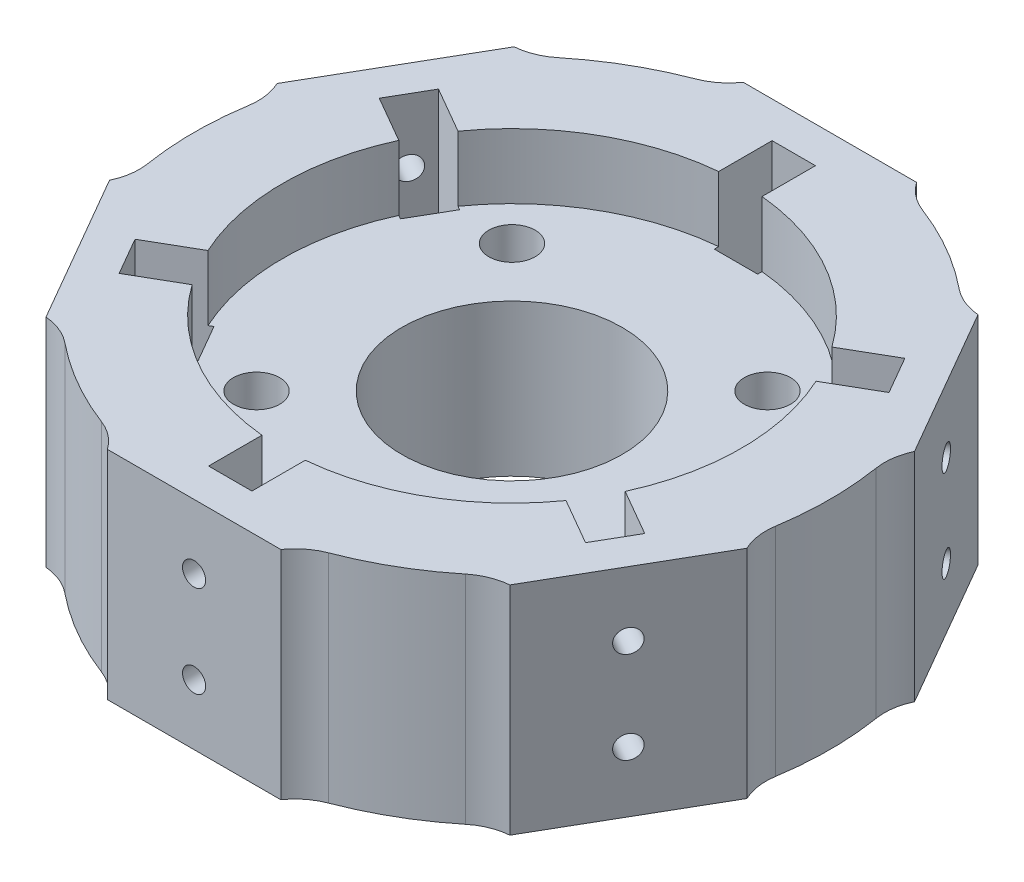
SolidWorks part; units mm, degrees
note: '?' marks a value the reader was unsure of.
material "PP Copolymer"
ref_plane "Front Plane" through (0, 0, 0) normal (0, 0, 1) x (1, 0, 0)
ref_plane "Top Plane" through (0, 0, 0) normal (0, 1, 0) x (1, 0, 0)
ref_plane "Right Plane" through (0, 0, 0) normal (1, 0, 0) x (0, 0, -1)
sketch "Sketch2" plane through (0, 0, 0) normal (0, 1, 0) x (1, 0, 0)
  line L0 (-12, 44) -> (12, 44)
  line L1 (-12, 44) -> (0, 0)
  line L2 (0, 0) -> (32.1051, 32.3923)
  line L3 (-2.875, 39) -> (2.875, 39) construction
  line L4 (-3.125, 38.75) -> (-3.125, 33.75) construction
  line L5 (-2.875, 33.5) -> (2.875, 33.5) construction
  line L6 (3.125, 38.75) -> (3.125, 33.75) construction
  line L7 (0, -44) -> (0, 44) construction
  line L9 (0, -16.5) -> (0, 16.5) construction
  arc A0 (12, 44) -> (15.7078, 41.1007) centre (18.5638, 48.5735) ccw
  arc A1 (32.1051, 32.3923) -> (27.7403, 34.1537) centre (32.784, 40.3634) cw
  arc A2 (15.7078, 41.1007) -> (27.7403, 34.1537) centre (0, 0) cw
  arc A3 (-3.125, 33.75) -> (-2.875, 33.5) centre (-2.875, 33.75) ccw construction
  arc A4 (2.875, 33.5) -> (3.125, 33.75) centre (2.875, 33.75) ccw construction
  arc A5 (2.875, 39) -> (3.125, 38.75) centre (2.875, 38.75) cw construction
  arc A6 (-2.875, 39) -> (-3.125, 38.75) centre (-2.875, 38.75) ccw construction
  circle A7 centre (0, 0) radius 45.607 construction
  point P19 (0, 0)
  point P20 (0, 39)
  dimension "D1" = 24
  dimension "D3" = 44
  dimension "D4" = 8
  dimension "D6" = 0.25
  dimension "D10" = 91.214
  dimension "D2" = 88
  dimension "D5" = 60
  dimension "D7" = 5.75
  dimension "D8" = 5
  dimension "D9" = 5
extrude "Boss-Extrude1" add sketch "Sketch2" against normal blind 30
hole_wizard "M3 Clearance Hole - Plastic Parts Only" positions "Sketch8" profile "Sketch9" hole size "M3" standard "ANSI Metric"
sketch "Sketch8" plane through (0, 0, -44) normal (0, 0, -1) x (-1, 0, 0)
  line L0 (0, -20.018) -> (0, -10.518) construction
  line L1 (0, -8.918) -> (0, 0) construction
  line L4 (0, -21.618) -> (0, -30) construction
  line L6 (0, -30) -> (0, -40.16) construction
  line L7 (-12, -30) -> (12, -30) construction
  circle A0 centre (0, -8.918) radius 1.6 construction
  circle A1 centre (0, -21.618) radius 1.6 construction
  point P0 (0, -8.918)
  point P2 (0, -21.618)
  dimension "D1" = 3.2
  dimension "D2" = 9.5
  dimension "D3" = 12.7
  dimension "D4" = 8.918
  dimension "D5" = 18.542
  dimension "D6" = 8.382
sketch "Sketch9" plane through (0, -8.918, -44) normal (1, 0, 0) x (0, 1, 0)
  line L0 (0, 0) -> (0, 10.9614)
  line L1 (0, 10.9614) -> (1.6, 10)
  line L2 (1.6, 10) -> (1.6, 0)
  line L5 (1.6, 0) -> (0, 0)
  line L10 (0, 10.9614) -> (-1.6, 10) construction
  line L11 (0, -6.35) -> (0, 107.95) construction
  dimension "Hole Dia." = 3.2
  dimension "Hole Depth" = 10
  dimension "Drill Angle" = 118
sketch "Sketch10" plane through (0, 0, -44) normal (0, 0, -1) x (-1, 0, 0)
  line L0 (-3, 0) -> (-3, -30)
  line L1 (2.75, -7.3303) -> (0, -5.7426) construction
  line L2 (0, -5.7426) -> (-2.75, -7.3303) construction
  line L3 (-2.75, -7.3303) -> (-2.75, -10.5057) construction
  line L4 (-2.75, -10.5057) -> (0, -12.0934) construction
  line L5 (0, -12.0934) -> (2.75, -10.5057) construction
  line L6 (2.75, -10.5057) -> (2.75, -7.3303) construction
  line L7 (2.75, -23.2057) -> (2.75, -20.0303) construction
  line L8 (2.75, -20.0303) -> (0, -18.4426) construction
  line L9 (0, -18.4426) -> (-2.75, -20.0303) construction
  line L10 (-2.75, -20.0303) -> (-2.75, -23.2057) construction
  line L11 (-2.75, -23.2057) -> (0, -24.7934) construction
  line L12 (0, -24.7934) -> (2.75, -23.2057) construction
  line L13 (-3, -30) -> (3, -30)
  line L14 (3, -30) -> (3, 0)
  line L15 (3, 0) -> (-3, 0)
  line L21 (-12, -30) -> (12, -30) construction
  circle A0 centre (0, -8.918) radius 2.75 construction
  circle A1 centre (0, -21.618) radius 2.75 construction
  point P25 (0, 0)
  dimension "D1" = 5.5
  dimension "D2" = 6
extrude "Wrench Clearance Slots - Plastic Parts Only" cut sketch "Sketch10" against normal blind 8 from offset 5 offset against normal yes
hole_wizard "M3x0.5 Tapped Hole - Metal Parts Only" [suppressed] positions "Sketch13" profile "Sketch14" tap size "M3x0.5" standard "ANSI Metric"
sketch "Sketch13" plane through (0, 0, -44) normal (0, 0, -1) x (-1, 0, 0)
  point P0 (0, -8.325)
  point P3 (0, -21.675)
sketch "Sketch14" plane through (0, -8.325, -44) normal (1, 0, 0) x (0, 1, 0)
  line L0 (0, 0) -> (0, 8.2517)
  line L1 (0, 8.2517) -> (1.25, 7.5006)
  line L2 (1.25, 7.5006) -> (1.25, 0.5)
  line L3 (1.25, 0.5) -> (1.75, 0)
  line L5 (1.75, 0) -> (0, 0)
  line L6 (-1.25, 0.5) -> (-1.75, 0) construction
  line L10 (0, 8.2517) -> (-1.25, 7.5006) construction
  line L11 (0, -6.35) -> (0, 107.95) construction
  dimension "Tap Drill Dia." = 2.5
  dimension "Tap Drill Depth" = 7.5006
  dimension "Near C'Sink Dia." = 3.5
  dimension "Near C'Sink Angle" = 90
  dimension "Drill Angle" = 118
cosmetic thread "Hole Thread3" [suppressed] parameters "D1"=5.9995, "D2"=3
cosmetic thread "Hole Thread4" [suppressed] parameters "D1"=5.9995, "D2"=3
ref_axis "Centerline" through (0, 1.5, 0) along (0, -1, 0)?
pattern_circular "Body Revolve - Plastic Parts Only" count 6 over 360 about axis through (0, 0, 0) along (0, 1, 0) of "Boss-Extrude1", "M3 Clearance Hole - Plastic Parts Only", "Wrench Clearance Slots - Plastic Parts Only"
pattern_circular "Body Revolve - Metal Parts Only" [suppressed] count 6 over 360 about axis through (0, 1.5, 0) along (0, -1, 0)
cosmetic thread "Hole Thread5" [suppressed] parameters "D1"=5.9995, "D2"=3
cosmetic thread "Hole Thread6" [suppressed] parameters "D1"=5.9995, "D2"=3
cosmetic thread "Hole Thread7" [suppressed] parameters "D1"=5.9995, "D2"=3
cosmetic thread "Hole Thread8" [suppressed] parameters "D1"=5.9995, "D2"=3
cosmetic thread "Hole Thread9" [suppressed] parameters "D1"=5.9995, "D2"=3
cosmetic thread "Hole Thread10" [suppressed] parameters "D1"=5.9995, "D2"=3
cosmetic thread "Hole Thread11" [suppressed] parameters "D1"=5.9995, "D2"=3
cosmetic thread "Hole Thread12" [suppressed] parameters "D1"=5.9995, "D2"=3
cosmetic thread "Hole Thread13" [suppressed] parameters "D1"=5.9995, "D2"=3
cosmetic thread "Hole Thread14" [suppressed] parameters "D1"=5.9995, "D2"=3
sketch "Sketch3" plane through (0, 0, 0) normal (0, 0, 1) x (1, 0, 0)
  line L0 (0, 0) -> (0, -30)
  line L1 (0, -30) -> (15.25, -30)
  line L2 (15.25, -30) -> (15.25, -9)
  line L3 (15.25, -9) -> (31.75, -9)
  line L4 (31.75, -9) -> (31.75, 0)
  line L5 (31.75, 0) -> (0, 0)
  line L7 (0, -948.6801) -> (0, 49051.3199) construction
  line L8 (0, 1.5) -> (0, -31.5) construction
  line L9 (-15.7078, -30) -> (-12, -30) construction
  line L10 (-25.3468, 0) -> (-28.3468, 0) construction
  dimension "D1" = 63.5
  dimension "D2" = 30.5
  dimension "D3" = 9
revolve "End of Arm Flange Clearance" cut sketch "Sketch3" angle 360 about L7
hole_wizard "Mounting Screws" positions "Sketch4" profile "Sketch5" counterbore size "M6" standard "ANSI Metric" end condition up to next
sketch "Sketch4" plane through (0, -30, 0) normal (0, -1, 0) x (-1, 0, 0)
  line L0 (-17.6777, -17.6777) -> (-17.6777, 17.6777) construction
  line L1 (-17.6777, 17.6777) -> (17.6777, 17.6777) construction
  line L2 (17.6777, 17.6777) -> (17.6777, -17.6777) construction
  line L6 (17.6777, -17.6777) -> (-17.6777, -17.6777) construction
  line L8 (0, -17.6777) -> (0, -25) construction
  circle A0 centre (0, 0) radius 25 construction
  point P0 (-17.6777, -17.6777)
  point P2 (-17.6777, 17.6777)
  point P4 (17.6777, 17.6777)
  point P6 (17.6777, -17.6777)
  dimension "D1" = 50
sketch "Sketch5" plane through (17.6777, -30, 17.6777) normal (1, 0, 0) x (0, 0, -1)
  line L0 (0, 0) -> (0, 21)
  line L1 (0, 21) -> (3.2, 21)
  line L3 (3.2, 21) -> (3.2, 6.5)
  line L4 (3.2, 6.5) -> (5.5, 6.5)
  line L5 (5.5, 6.5) -> (5.5, 0)
  line L7 (5.5, 0) -> (0, 0)
  line L11 (0, -6.35) -> (0, 107.95) construction
  dimension "Thru Hole Dia." = 6.4
  dimension "Thru Hole Depth" = 21
  dimension "C'Bore Dia." = 11
  dimension "C'Bore Depth" = 6.5
hole_wizard "Locating Pin" positions "Sketch6" profile "Sketch7" hole size "Ø6.0" standard "ANSI Metric" end condition up to next
sketch "Sketch6" plane through (0, -30, 0) normal (0, -1, 0) x (-1, 0, 0)
  circle A0 centre (0, 0) radius 25 construction
  point P2 (0, -25)
sketch "Sketch7" plane through (0, -30, 25) normal (1, 0, 0) x (0, 0, -1)
  line L0 (0, 0) -> (0, 21)
  line L1 (0, 21) -> (3.15, 21)
  line L2 (3.15, 21) -> (3.15, 0)
  line L5 (3.15, 0) -> (0, 0)
  line L11 (0, -6.35) -> (0, 107.95) construction
  dimension "Thru Hole Dia." = 6.3
  dimension "Thru Hole Depth" = 21
sketch "Sketch11" [suppressed] plane through (0, 0, 0) normal (0, 1, 0) x (1, 0, 0)
  line L0 (-32.3923, 32.1051) -> (-11.6077, 44.1051) construction
  line L1 (-24.7063, 36.5426) -> (-19.2937, 39.6676) construction
  line L2 (-24.7063, 36.5426) -> (-18.4414, 25.6915) construction
  line L3 (-18.4414, 25.6915) -> (-13.0288, 28.8165) construction
  line L4 (-19.2937, 39.6676) -> (-13.0288, 28.8165) construction
  line L5 (-22.0813, 31.996) -> (-19.5813, 27.6659) construction
  line L6 (-16.6687, 35.121) -> (-14.1687, 30.7909) construction
  line L7 (19.2937, 39.6676) -> (24.7063, 36.5426) construction
  line L8 (19.2937, 39.6676) -> (13.0288, 28.8165) construction
  line L9 (13.0288, 28.8165) -> (18.4414, 25.6915) construction
  line L10 (24.7063, 36.5426) -> (18.4414, 25.6915) construction
  line L11 (44, 3.125) -> (44, -3.125) construction
  line L12 (44, 3.125) -> (31.4702, 3.125) construction
  line L13 (31.4702, 3.125) -> (31.4702, -3.125) construction
  line L14 (44, -3.125) -> (31.4702, -3.125) construction
  line L15 (24.7063, -36.5426) -> (19.2937, -39.6676) construction
  line L16 (24.7063, -36.5426) -> (18.4414, -25.6915) construction
  line L17 (18.4414, -25.6915) -> (13.0288, -28.8165) construction
  line L18 (19.2937, -39.6676) -> (13.0288, -28.8165) construction
  line L19 (-19.2937, -39.6676) -> (-24.7063, -36.5426) construction
  line L20 (-19.2937, -39.6676) -> (-13.0288, -28.8165) construction
  line L21 (-13.0288, -28.8165) -> (-18.4414, -25.6915) construction
  line L22 (-24.7063, -36.5426) -> (-18.4414, -25.6915) construction
  line L23 (-44, -3.125) -> (-44, 3.125) construction
  line L24 (-44, -3.125) -> (-31.4702, -3.125) construction
  line L25 (-31.4702, -3.125) -> (-31.4702, 3.125) construction
  line L26 (-44, 3.125) -> (-31.4702, 3.125) construction
  line L27 (-13.0288, 28.8165) -> (13.0288, 28.8165)
  line L28 (-15.7351, 27.254) -> (0, 0) construction
  line L29 (0, 0) -> (15.7351, 27.254) construction
  line L30 (0, 41.46) -> (0, 44) construction
  arc A0 (-13.0288, 28.8165) -> (13.0288, 28.8165) centre (0, 28.4253) cw
  circle A1 centre (0, 0) radius 31.625 construction
  arc A2 (6.947, 43.4481) -> (-6.947, 43.4481) centre (0, 0) ccw construction
  point P15 (22, 38.1051)
  point P37 (0, 0)
  point P44 (0, 44)
  dimension "D3" = 13.0347
  dimension "D2" = 2.54
  dimension "D1" = 6
extrude "Lightnening Cut - Walls - Metal Parts Only" [suppressed] cut sketch "Sketch11" against normal up to surface (9 mm away)
pattern_circular "Ligntening Cut - Walls - Pattern - Metal Parts Only" [suppressed] count 6 over 360
sketch "Sketch12" [suppressed] plane through (0, -9, 0) normal (0, 1, 0) x (1, 0, 0)
  line L0 (5.5433, -22.7039) -> (11.662, -20.1694) construction
  arc A5 (13.0288, 28.8165) -> (11.5791, 19.9267) centre (-10.6033, 28.107) cw
  arc A6 (-11.5791, -19.9267) -> (-13.0288, -28.8165) centre (10.6033, -28.107) ccw
  arc A12 (-11.5791, -19.9267) -> (-23.8705, -19.6521) centre (-17.6777, -17.6777) ccw
  circle A13 centre (8.6026, -21.4367) radius 3.3114 construction
  arc A14 (23.8705, -19.6521) -> (11.5791, -19.9267) centre (17.6777, -17.6777) ccw
  arc A15 (11.5791, 19.9267) -> (23.8705, 19.6521) centre (17.6777, 17.6777) ccw
  arc A16 (-23.8705, 19.6521) -> (-11.5791, 19.9267) centre (-17.6777, 17.6777) ccw
  arc A17 (-11.5791, 19.9267) -> (-23.8705, 19.6521) centre (-17.6777, 17.6777) ccw construction
  arc A19 (23.8705, 19.6521) -> (11.5791, 19.9267) centre (17.6777, 17.6777) ccw construction
  arc A20 (11.5791, -19.9267) -> (23.8705, -19.6521) centre (17.6777, -17.6777) ccw construction
  circle A21 centre (0, -25) radius 6
  arc A22 (-23.8705, -19.6521) -> (-11.5791, -19.9267) centre (-17.6777, -17.6777) ccw construction
  arc A23 (-31.1342, 25.5011) -> (-31.4702, 3.125) centre (-24.6171, 14.2127) ccw
  arc A38 (-31.1342, -25.5011) -> (-18.4414, -25.6915) centre (-24.6171, -14.2127) ccw construction
  arc A39 (31.4702, -3.125) -> (31.4702, 3.125) centre (0, 0) ccw
  arc A48 (31.4702, 3.125) -> (18.4414, 25.6915) centre (24.6171, 14.2127) ccw
  arc A49 (18.4414, 25.6915) -> (13.0288, 28.8165) centre (0, 0) ccw
  arc A50 (13.0288, 28.8165) -> (-13.0288, 28.8165) centre (0, 28.4253) ccw
  arc A51 (-13.0288, 28.8165) -> (-18.4414, 25.6915) centre (0, 0) ccw
  arc A52 (-18.4414, 25.6915) -> (-31.4702, 3.125) centre (-24.6171, 14.2127) ccw
  arc A53 (-31.4702, 3.125) -> (-31.4702, -3.125) centre (0, 0) ccw
  arc A54 (-31.4702, -3.125) -> (-18.4414, -25.6915) centre (-24.6171, -14.2127) ccw
  arc A55 (-18.4414, -25.6915) -> (-13.0288, -28.8165) centre (0, 0) ccw
  arc A56 (-13.0288, -28.8165) -> (13.0288, -28.8165) centre (0, -28.4253) ccw
  arc A57 (13.0288, -28.8165) -> (18.4414, -25.6915) centre (0, 0) ccw
  arc A58 (18.4414, -25.6915) -> (31.4702, -3.125) centre (24.6171, -14.2127) ccw
  arc A59 (31.4702, -3.125) -> (31.4702, 3.125) centre (0, 0) ccw
  arc A60 (31.4702, 3.125) -> (31.1342, 25.5011) centre (24.6171, 14.2127) ccw
  arc A61 (18.4414, 25.6915) -> (13.0288, 28.8165) centre (0, 0) ccw construction
  arc A62 (13.0288, 28.8165) -> (-13.0288, 28.8165) centre (0, 28.4253) ccw
  arc A63 (-13.0288, 28.8165) -> (-18.4414, 25.6915) centre (0, 0) ccw construction
  arc A64 (-18.4414, 25.6915) -> (-31.1342, 25.5011) centre (-24.6171, 14.2127) ccw construction
  arc A67 (-31.4702, 3.125) -> (-31.4702, -3.125) centre (0, 0) ccw
  arc A68 (-31.4702, -3.125) -> (-31.1342, -25.5011) centre (-24.6171, -14.2127) ccw
  arc A69 (-18.4414, -25.6915) -> (-13.0288, -28.8165) centre (0, 0) ccw construction
  arc A70 (-13.0288, -28.8165) -> (13.0288, -28.8165) centre (0, -28.4253) ccw
  arc A71 (13.0288, -28.8165) -> (18.4414, -25.6915) centre (0, 0) ccw construction
  arc A72 (18.4414, -25.6915) -> (31.1342, -25.5011) centre (24.6171, -14.2127) ccw construction
  arc A73 (31.1342, -25.5011) -> (31.4702, -3.125) centre (24.6171, -14.2127) ccw
  arc A74 (31.1342, 25.5011) -> (18.4414, 25.6915) centre (24.6171, 14.2127) ccw construction
  arc A75 (-13.0288, 28.8165) -> (-11.5791, 19.9267) centre (10.6033, 28.107) ccw
  circle A76 centre (-17.6777, 17.6777) radius 3.2 construction
  arc A77 (-23.8705, -19.6521) -> (-31.1342, -25.5011) centre (-28.6343, -21.171) cw
  arc A78 (-31.1342, 25.5011) -> (-23.8705, 19.6521) centre (-28.6343, 21.171) cw
  arc A79 (11.5791, -19.9267) -> (13.0288, -28.8165) centre (-10.6033, -28.107) cw
  arc A80 (31.1342, -25.5011) -> (23.8705, -19.6521) centre (28.6343, -21.171) cw
  arc A81 (31.1342, 25.5011) -> (23.8705, 19.6521) centre (28.6343, 21.171) ccw
  circle A82 centre (0, -25) radius 3 construction
  dimension "D2" = 3.3
  dimension "D3" = 5
  dimension "D4" = 3
  dimension "D5" = 6.6229
  dimension "D1" = 0
extrude "Lightening Cut - Floor - Metal Parts Only" [suppressed] cut sketch "Sketch12" against normal offset from surface (13 mm away) 8
